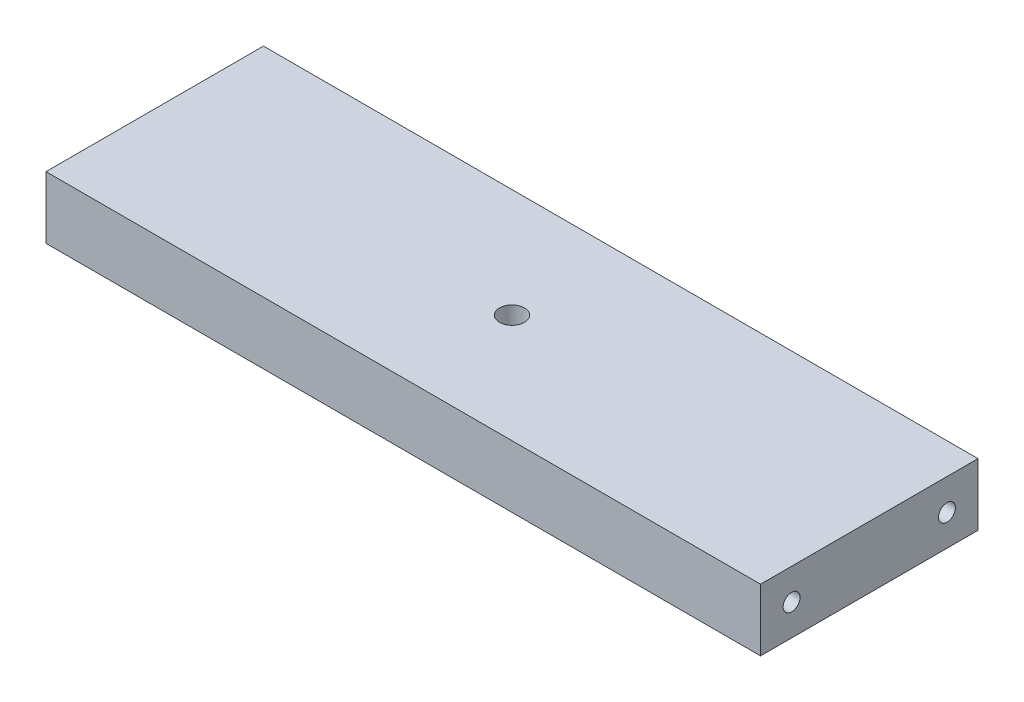
SolidWorks part; units mm, degrees
material "6061 Alloy"
ref_plane "Front Plane" through (0, 0, 0) normal (0, 0, 1) x (1, 0, 0)
ref_plane "Top Plane" through (0, 0, 0) normal (0, 1, 0) x (1, 0, 0)
ref_plane "Right Plane" through (0, 0, 0) normal (1, 0, 0) x (0, 0, -1)
sketch "Sketch2" plane through (0, 0, 0) normal (0, 1, 0) x (1, 0, 0)
  line L1 (-73.025, -22.225) -> (73.025, -22.225)
  line L2 (-73.025, -22.225) -> (-73.025, 22.225)
  line L3 (-73.025, 22.225) -> (73.025, 22.225)
  line L4 (73.025, -22.225) -> (73.025, 22.225)
  line L5 (-73.025, -22.225) -> (73.025, 22.225) construction
  line L6 (-73.025, 22.225) -> (73.025, -22.225) construction
  point P0 (0, 0)
  dimension "D1" = 146.05
  dimension "D2" = 44.45
extrude "Boss-Extrude1" add sketch "Sketch2" along normal blind 12.7
hole_wizard "1/4-20 Tapped Hole1" positions "Sketch4" profile "Sketch5" tap size "1/4-20" standard "ANSI Inch" end condition through all
sketch "Sketch4" plane through (0, 0, 0) normal (0, -1, 0) x (-1, 0, 0)
  point P0 (0, 0)
sketch "Sketch5" plane through (0, 0, 0) normal (1, 0, 0) x (0, 0, -1)
  line L0 (0, 0) -> (0, 12.7)
  line L1 (0, 12.7) -> (2.5527, 12.7)
  line L2 (2.5527, 12.7) -> (2.5527, 0)
  line L5 (2.5527, 0) -> (0, 0)
  line L11 (0, -6.35) -> (0, 107.95) construction
  dimension "Thru Tap Drill Dia." = 5.1054
  dimension "Thru Tap Drill Depth" = 12.7
cosmetic thread "Hole Thread1" parameters "D2"=6.35
hole_wizard "#8-32 Tapped Hole1" positions "Sketch6" profile "Sketch7" tap size "#8-32" standard "ANSI Inch"
sketch "Sketch6" plane through (-73.025, 0, 0) normal (-1, 0, 0) x (0, 0, 1)
  line L0 (-22.225, 12.7) -> (-22.225, 0) construction
  line L1 (22.225, 12.7) -> (22.225, 0) construction
  line L2 (-22.225, 0) -> (22.225, 0) construction
  point P0 (-15.875, 6.35)
  point P2 (15.875, 6.35)
  dimension "D1" = 6.35
  dimension "D2" = 6.35
  dimension "D3" = 6.35
  dimension "D4" = 6.35
sketch "Sketch7" plane through (-73.025, 6.35, -15.875) normal (0, 1, 0) x (0, 0, 1)
  line L0 (0, 0) -> (0, 7.3878)
  line L1 (0, 7.3878) -> (1.7272, 6.35)
  line L2 (1.7272, 6.35) -> (1.7272, 0)
  line L5 (1.7272, 0) -> (0, 0)
  line L10 (0, 7.3878) -> (-1.7272, 6.35) construction
  line L11 (0, -6.35) -> (0, 107.95) construction
  dimension "Tap Drill Dia." = 3.4544
  dimension "Tap Drill Depth" = 6.35
  dimension "Drill Angle" = 118
cosmetic thread "Hole Thread2" parameters "D1"=6.35, "D2"=4.1656
cosmetic thread "Hole Thread3" parameters "D1"=6.35, "D2"=4.1656
mirror "Mirror1" about plane through (0, 0, 0) normal (1, 0, 0) of "#8-32 Tapped Hole1"
